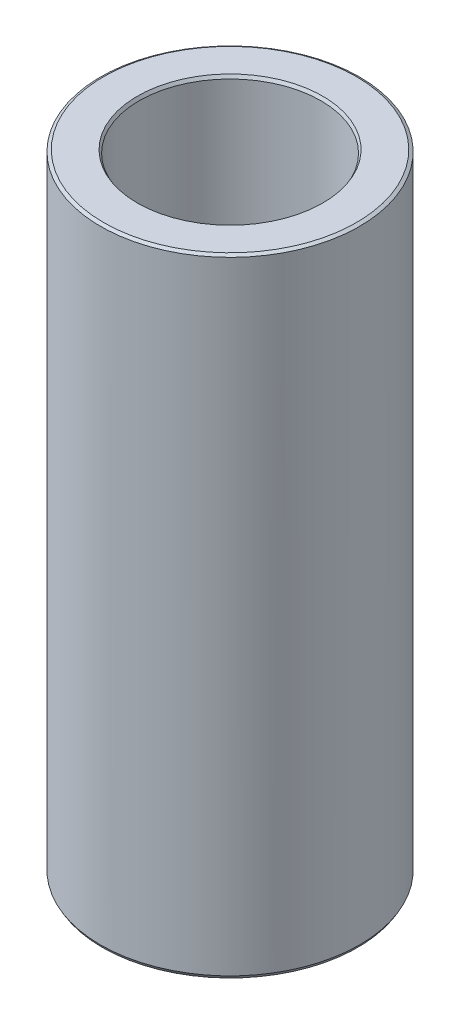
SolidWorks part; units mm, degrees
ref_plane "Front Plane" through (0, 0, 0) normal (0, 0, 1) x (1, 0, 0)
ref_plane "Top Plane" through (0, 0, 0) normal (0, 1, 0) x (1, 0, 0)
ref_plane "Right Plane" through (0, 0, 0) normal (1, 0, 0) x (0, 0, -1)
sketch "Sketch1" plane through (0, 0, 0) normal (0, 1, 0) x (1, 0, 0)
  circle A0 centre (0, 0) radius 52.5
  dimension "SLEEVE_OD" = 105
extrude "Boss-Extrude1" add sketch "Sketch1" along normal blind 254.2789
sketch "Sketch2" plane through (0, 0, 0) normal (0, 1, 0) x (1, 0, 0)
  circle A0 centre (0, 0) radius 36.8467
  dimension "BORE_D" = 73.6934
extrude "Cut-Extrude1" cut sketch "Sketch2" along normal through all
chamfer "Chamfer1" distance 0.7216 angle 60 4 edges at (0, 254.2789, 36.8467) (0, 0, 36.8467) (0, 0, 52.5) (0, 254.2789, 52.5) first distance on face at (0, 254.2789, 36.8467) first distance on face at (0, 0, 36.8467) first distance on face at (0, 254.2789, 52.5)
